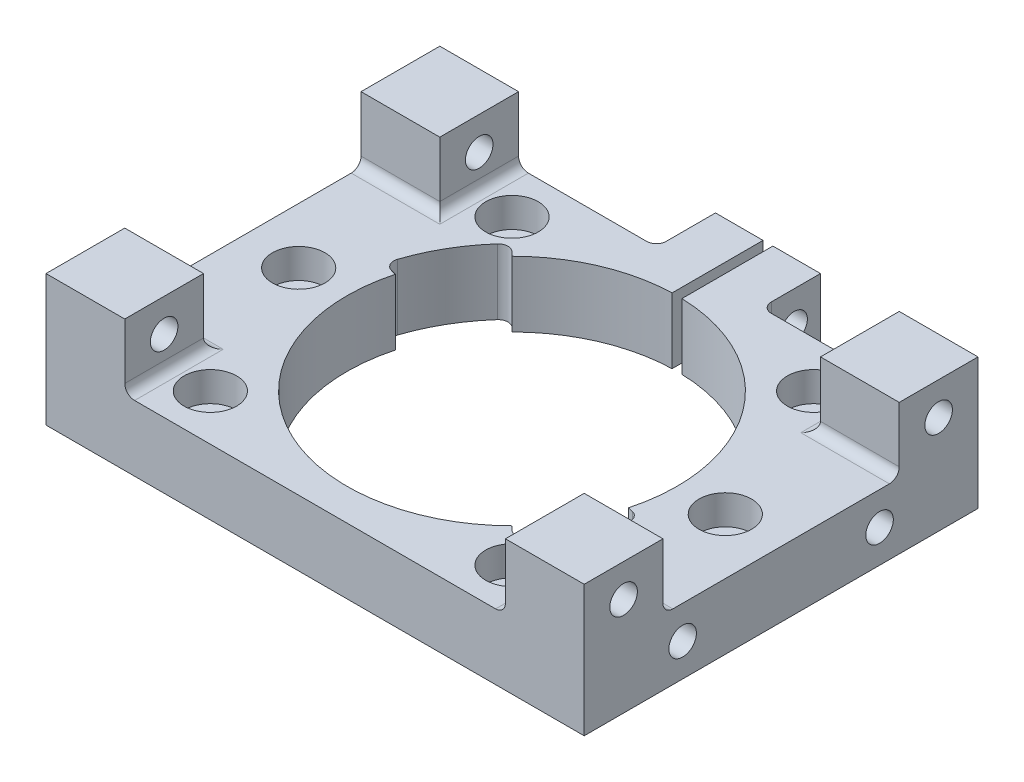
SolidWorks part; units mm, degrees
material "6061 Alloy"
ref_plane "Front Plane" through (0, 0, 0) normal (0, 0, 1) x (1, 0, 0)
ref_plane "Top Plane" through (0, 0, 0) normal (0, 1, 0) x (1, 0, 0)
ref_plane "Right Plane" through (0, 0, 0) normal (1, 0, 0) x (0, 0, -1)
sketch "Sketch1" plane through (0, 76, 0) normal (0, 1, 0) x (1, 0, 0)
  line L0 (-18.3542, 18.3542) -> (18.3542, -18.3542)
  line L1 (-41, -30) -> (41, -30)
  line L2 (-41, -30) -> (-41, 30)
  line L3 (-41, 30) -> (41, 30)
  line L4 (41, -30) -> (41, 30)
  line L5 (-41, -30) -> (41, 30) construction
  line L6 (-41, 30) -> (41, -30) construction
  line L7 (-25.0722, 6.7181) -> (25.0722, -6.7181)
  line L8 (-103.759, 0) -> (103.759, 0) construction
  circle A0 centre (0, 0) radius 25.15
  arc A1 (-20.5349, 18.2912) -> (-26.1081, 8.6381) centre (0, 0) ccw
  arc A2 (26.1081, -8.6381) -> (20.5349, -18.2912) centre (0, 0) cw
  circle A3 centre (0, 0) radius 27.5 construction
  arc A4 (18.3542, -18.3542) -> (20.5349, -18.2912) centre (19.4148, -17.2935) ccw
  arc A5 (25.0722, -6.7181) -> (26.1081, -8.6381) centre (24.684, -8.167) cw
  arc A6 (-25.0722, 6.7181) -> (-26.1081, 8.6381) centre (-24.684, 8.167) cw
  arc A7 (-18.3542, 18.3542) -> (-20.5349, 18.2912) centre (-19.4148, 17.2935) ccw
  circle A8 centre (22.981, 22.981) radius 2 construction
  circle A9 centre (32.5, 0) radius 2 construction
  circle A10 centre (22.981, -22.981) radius 2 construction
  circle A11 centre (-22.981, -22.981) radius 2 construction
  circle A12 centre (-32.5, 0) radius 2 construction
  circle A13 centre (-22.981, 22.981) radius 2 construction
  circle A14 centre (22.981, 22.981) radius 2
  circle A15 centre (32.5, 0) radius 2
  circle A16 centre (22.981, -22.981) radius 2
  circle A17 centre (-22.981, -22.981) radius 2
  circle A18 centre (-32.5, 0) radius 2
  circle A19 centre (-22.981, 22.981) radius 2
  point P0 (0, 0)
  dimension "D1" = 50.3
  dimension "D4" = 1.5
  dimension "D2" = 45
  dimension "D3" = 15
  dimension "D5" = 82
  dimension "D6" = 60
extrude "Boss-Extrude1" add sketch "Sketch1" along normal blind 10 contours L1 L4 L3 L2 A19 A18 A17 A16 A15 A14 A7 L0 A0 L7 A5 A2 A4 A6 A1 region at (-39.9839, 76, 0)
sketch "Sketch2" plane through (0, 86, 0) normal (0, 1, 0) x (1, 0, 0)
  line L0 (0, -142.3844) -> (0, 142.3844) construction
  line L1 (-8, 39) -> (8, 39)
  line L2 (-8, 39) -> (-8, 30)
  line L3 (-8, 30) -> (8, 30)
  line L4 (8, 39) -> (8, 30)
  line L5 (-8, 39) -> (8, 30) construction
  line L6 (-8, 30) -> (8, 39) construction
  line L7 (-41, 30) -> (41, 30) construction
  point P0 (0, 34.5)
  dimension "D1" = 9
  dimension "D2" = 16
extrude "Boss-Extrude2" add sketch "Sketch2" against normal blind 10
sketch "Sketch3" plane through (0, 86, 0) normal (0, 1, 0) x (1, 0, 0)
  line L0 (0, -142.3844) -> (0, 142.3844) construction
  line L1 (-0.75, 25) -> (0.75, 25)
  line L2 (-0.75, 25) -> (-0.75, 39)
  line L3 (-0.75, 39) -> (0.75, 39)
  line L4 (0.75, 25) -> (0.75, 39)
  line L5 (-0.75, 25) -> (0.75, 39) construction
  line L6 (-0.75, 39) -> (0.75, 25) construction
  line L7 (8, 39) -> (-8, 39) construction
  point P0 (0, 32)
  dimension "D1" = 14
  dimension "D2" = 1.5
extrude "Cut-Extrude1" cut sketch "Sketch3" against normal blind 10
sketch "Sketch4" plane through (8, 0, 0) normal (1, 0, 0) x (0, 0, -1)
  line L0 (35, 81) -> (39, 81) construction
  line L1 (39, 76) -> (39, 86) construction
  circle A0 centre (35, 81) radius 2
  dimension "D1" = 4
  dimension "D2" = 4
extrude "Cut-Extrude2" cut sketch "Sketch4" against normal up to vertex (7.25 mm away) up to point (0.75, 86, -39)
sketch "Sketch5" plane through (-0.75, 0, 0) normal (1, 0, 0) x (0, 0, -1)
  circle A0 centre (35, 81) radius 1.6
  dimension "D1" = 3.2
extrude "Cut-Extrude3" cut sketch "Sketch5" against normal blind 10
sketch "Sketch7" plane through (0, 86, 0) normal (0, 1, 0) x (1, 0, 0)
  circle A0 centre (-22.981, 22.981) radius 4
  circle A1 centre (22.981, 22.981) radius 4
  circle A2 centre (32.5, 0) radius 4
  circle A3 centre (-32.5, 0) radius 4
  circle A4 centre (-22.981, -22.981) radius 4
  circle A5 centre (22.981, -22.981) radius 4
  dimension "D1" = 8
extrude "Cut-Extrude4" cut sketch "Sketch7" against normal blind 4.5
fillet "Fillet1" radius 1.5 2 edges at (-8, 81, -30) (8, 81, -30)
sketch "Sketch8" plane through (0, 86, 0) normal (0, 1, 0) x (1, 0, 0)
  line L0 (9.4279, 0) -> (0, 0) construction
  line L1 (-41, 30) -> (-29, 30)
  line L2 (-41, 30) -> (-41, 18)
  line L3 (-41, 18) -> (-29, 18)
  line L4 (-29, 30) -> (-29, 18)
  line L5 (0, 0) -> (0, 11.3596) construction
  line L6 (29, 30) -> (29, 18)
  line L7 (41, 18) -> (29, 18)
  line L8 (41, 30) -> (41, 18)
  line L9 (41, 30) -> (29, 30)
  line L10 (41, -30) -> (29, -30)
  line L11 (41, -30) -> (41, -18)
  line L12 (41, -18) -> (29, -18)
  line L13 (29, -30) -> (29, -18)
  line L14 (-29, -30) -> (-29, -18)
  line L15 (-41, -18) -> (-29, -18)
  line L16 (-41, -30) -> (-41, -18)
  line L17 (-41, -30) -> (-29, -30)
  dimension "D1" = 12
  dimension "D2" = 12
extrude "Boss-Extrude3" add sketch "Sketch8" along normal blind 10
fillet "Fillet2" radius 1.5 8 edges at (35, 86, 18) (-35, 86, 18) (-29, 86, 24) (29, 86, 24) (29, 86, -24) (35, 86, -18) (-35, 86, -18) (-29, 86, -24)
sketch "Sketch9" plane through (-41, 0, 0) normal (-1, 0, 0) x (0, 0, 1)
  line L0 (0, 86) -> (0, 76) construction
  line L1 (16.5, 86) -> (-16.5, 86) construction
  line L2 (30, 76) -> (-30, 76) construction
  line L3 (-30, 96) -> (-18, 96) construction
  line L4 (-30, 96) -> (-30, 76) construction
  circle A0 centre (-24, 91) radius 2.1
  circle A1 centre (-15, 81) radius 2.1
  circle A2 centre (15, 81) radius 2.1
  circle A3 centre (24, 91) radius 2.1
  dimension "D2" = 6
  dimension "D3" = 15
  dimension "D4" = 5
  dimension "D5" = 4.2
  dimension "D1" = 5
extrude "Cut-Extrude5" cut sketch "Sketch9" against normal blind 12
mirror "Mirror1" about plane through (0, 0, 0) normal (1, 0, 0) of "Cut-Extrude5"
